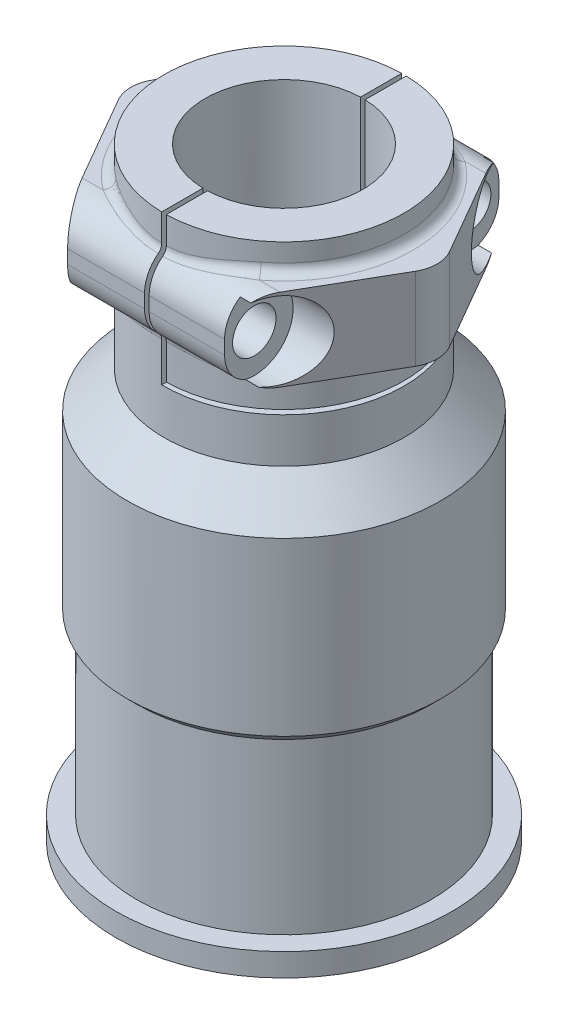
SolidWorks part; units mm, degrees
ref_plane "Alzado" through (0, 0, 0) normal (0, 0, 1) x (1, 0, 0)
ref_plane "Planta" through (0, 0, 0) normal (0, 1, 0) x (1, 0, 0)
ref_plane "Vista lateral" through (0, 0, 0) normal (1, 0, 0) x (0, 0, -1)
sketch "Croquis1" plane through (0, 0, 0) normal (0, 1, 0) x (1, 0, 0)
  circle A0 centre (0, 0) radius 7.35
  dimension "D1" = 14.7
extrude "Saliente-Extruir1" add sketch "Croquis1" along normal blind 1
sketch "Croquis2" plane through (0, 1, 0) normal (0, 1, 0) x (1, 0, 0)
  circle A0 centre (0, 0) radius 6.45
  dimension "D1" = 12.9
extrude "Saliente-Extruir2" add sketch "Croquis2" along normal blind 11.4
sketch "Croquis3" plane through (0, 12.4, 0) normal (0, 1, 0) x (1, 0, 0)
  circle A0 centre (0, 0) radius 6.85
  dimension "D1" = 13.7
extrude "Saliente-Extruir3" add sketch "Croquis3" along normal blind 5.5
chamfer "Chaflán1" distance 4 angle 45 1 edges at (0, 12.4, 6.45)
sketch "Croquis4" plane through (0, 17.9, 0) normal (0, 1, 0) x (1, 0, 0)
  circle A0 centre (0, 0) radius 5.25
  dimension "D1" = 10.5
extrude "Saliente-Extruir4" add sketch "Croquis4" along normal blind 3.7
sketch "Croquis6" plane through (0, 21.6, 0) normal (0, 1, 0) x (1, 0, 0)
  line L1 (6.9282, 0) -> (3.4641, 6)
  line L2 (3.4641, 6) -> (-3.4641, 6)
  line L3 (-3.4641, 6) -> (-6.9282, 0)
  line L4 (-6.9282, 0) -> (-3.4641, -6)
  line L5 (-3.4641, -6) -> (3.4641, -6)
  line L6 (3.4641, -6) -> (6.9282, 0)
  circle A0 centre (0, 0) radius 6 construction
  dimension "D1" = 12
extrude "Saliente-Extruir5" add sketch "Croquis6" along normal blind 3.6
sketch "Croquis7" plane through (0, 25.2, 0) normal (0, 1, 0) x (1, 0, 0)
  circle A0 centre (0, 0) radius 5.25 construction
  circle A1 centre (0, 0) radius 5.25
extrude "Saliente-Extruir6" add sketch "Croquis7" along normal blind 1.2
sketch "Croquis8" plane through (0, 0, 0) normal (0, 0, 1) x (1, 0, 0)
  line L0 (0, 0) -> (0, 44.0021)
  line L1 (0, 44.0021) -> (-3.45, 44.0021)
  line L2 (-3.45, 44.0021) -> (-3.45, 17.9461)
  line L3 (-3.45, 17.9461) -> (-5.85, 16.5)
  line L4 (-5.85, 16.5) -> (-5.85, 0)
  line L5 (-5.85, 0) -> (0, 0)
  line L6 (-5.25, 21.6) -> (-5.25, 17.9) construction
  dimension "D1" = 1.8
  dimension "D2" = 1.5
  dimension "D3" = 16.5
revolve "Cortar-Revolución1" cut sketch "Croquis8" angle 360 about L0
sketch "Croquis9" plane through (0, 26.4, 0) normal (0, 1, 0) x (1, 0, 0)
  line L1 (0.1, 81.2518) -> (-0.1, 81.2518)
  line L2 (0.1, 81.2518) -> (0.1, -81.2518)
  line L3 (0.1, -81.2518) -> (-0.1, -81.2518)
  line L4 (-0.1, 81.2518) -> (-0.1, -81.2518)
  line L5 (0.1, 81.2518) -> (-0.1, -81.2518) construction
  line L6 (0.1, -81.2518) -> (-0.1, 81.2518) construction
  point P0 (0, 0)
  dimension "D1" = 0.2
extrude "Cortar-Extruir1" cut sketch "Croquis9" against normal blind 6.55
sketch "Croquis10" plane through (0.1, 0, 0) normal (-1, 0, 0) x (0, 0, 1)
  line L1 (-5.249, 19.85) -> (54.5536, 19.85)
  line L2 (-5.249, 19.85) -> (-5.249, 20.05)
  line L3 (-5.249, 20.05) -> (54.5536, 20.05)
  line L4 (54.5536, 19.85) -> (54.5536, 20.05)
  dimension "D1" = 0.2
extrude "Cortar-Extruir2" cut sketch "Croquis10" against normal blind 6.55
ref_plane "Plano4" through (6.9, 0, 0) normal (-1, 0, 0) x (0, 0, 1)
sketch "Croquis11" plane through (6.9, 0, 0) normal (-1, 0, 0) x (0, 0, 1)
  line L0 (-4.7, 23.3753) -> (4.7, 23.3753) construction
  line L1 (0, 23.3753) -> (0, 26.4) construction
  line L2 (3.4486, 26.4) -> (-3.4486, 26.4) construction
  circle A0 centre (-4.7, 23.3753) radius 0.95
  circle A1 centre (4.7, 23.3753) radius 0.95
  dimension "D1" = 1.9
  dimension "D2" = 4.7
  dimension "D3" = 4.7
hole_wizard "Taladro roscado M2.2x0.451" positions "Croquis3D2" profile "Croquis15" tap size "M2.2x0.45" standard "Ansi Metric"
sketch3d "Croquis3D2"
  point P0 (6.9, 23.3753, 4.7)
  point P3 (6.9, 23.3753, -4.7)
sketch "Croquis15" plane through (6.9, 23.3753, 4.7) normal (0, 1, 0) x (0, 0, -1)
  line L0 (0, 0) -> (0, 14.25)
  line L1 (0, 14.25) -> (0.875, 14.25)
  line L2 (0.875, 14.25) -> (0.875, 0)
  line L5 (0.875, 0) -> (0, 0)
  line L11 (0, -6.35) -> (0, 107.95) construction
  dimension "Diámetro de perforador para roscar hasta el siguiente" = 1.75
  dimension "Profundidad de perforador para roscar hasta el siguiente" = 14.25
cosmetic thread "Rosca de taladro1" parameters "D2"=2.2
cosmetic thread "Rosca de taladro2" parameters "D2"=2.2
extrude "Cortar-Extruir3" cut sketch "Croquis11" along normal blind 6.9 contours A1
sketch3d "Croquis3D3"
  point P0 (0.1, 21.4024, -4.7562)
sketch "Croquis16" plane through (6.9, 0, 0) normal (-1, 0, 0) x (0, 0, 1)
  circle A0 centre (4.7, 23.3753) radius 1.7
  circle A1 centre (-4.7, 23.3753) radius 1.7
  dimension "D1" = 3.4
extrude "Cortar-Extruir4" cut sketch "Croquis16" along normal blind 3.5
chamfer "Chaflán2" distance 1.6 angle 45 1 edges at (0, 17.9, 6.85)
fillet "Redondeo3" radius 1.5 4 edges at (1.7821, 21.6, -6) (1.7821, 25.2, -6) (1.7821, 21.6, 6) (1.7821, 25.2, 6)
fillet "Redondeo4" radius 1.5 4 edges at (-1.7821, 21.6, -6) (-1.7821, 25.2, -6) (-1.7821, 21.6, 6) (-1.7821, 25.2, 6)
fillet "Redondeo5" radius 1.5 1 edges at (-6.9282, 23.4, 0)
fillet "Redondeo6" radius 1.5 1 edges at (6.9282, 23.4, 0)
fillet "Redondeo7" radius 0.4 3 edges at (1.5944, 25.1135, 5.002) (1.3339, 25.0843, -5.0777) (5.25, 25.2, 0)
fillet "Redondeo8" radius 0.4 3 edges at (-1.5944, 25.1135, -5.002) (-1.3339, 25.0843, 5.0777) (-5.25, 25.2, 0)
fillet "Redondeo9" radius 0.4 3 edges at (-1.3339, 21.7157, -5.0777) (-1.5944, 21.6865, 5.002) (-5.25, 21.6, 0)
fillet "Redondeo10" radius 0.4 3 edges at (1.3339, 21.7157, 5.0777) (1.5944, 21.6865, -5.002) (5.25, 21.6, 0)
